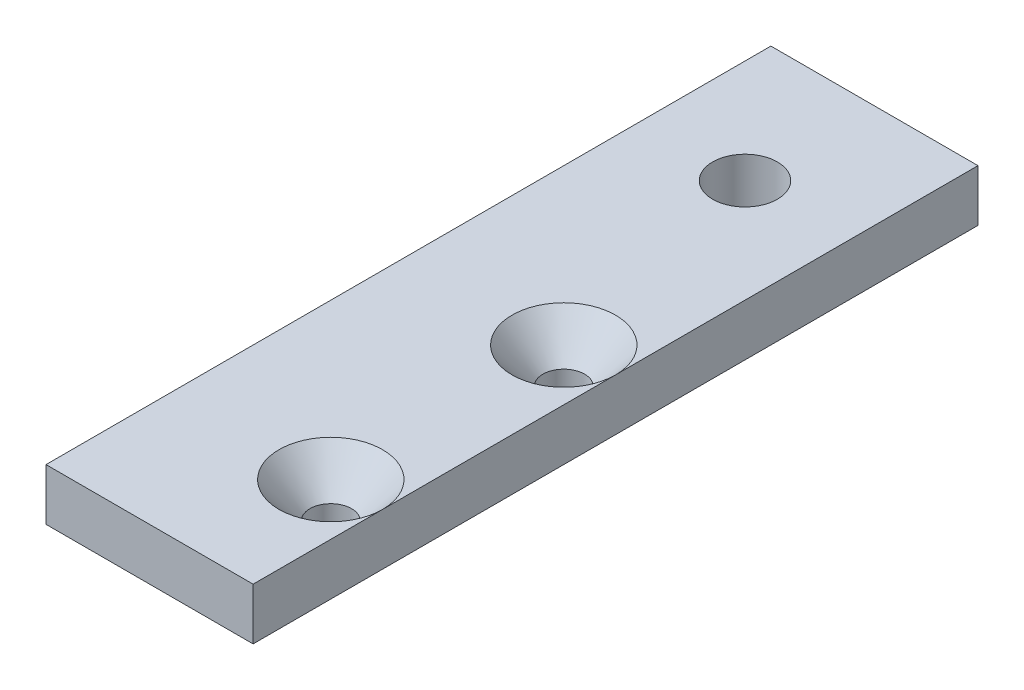
SolidWorks part; units mm, degrees
material "6061 Alloy"
ref_plane "Front Plane" through (0, 0, 0) normal (0, 0, 1) x (1, 0, 0)
ref_plane "Top Plane" through (0, 0, 0) normal (0, 1, 0) x (1, 0, 0)
ref_plane "Right Plane" through (0, 0, 0) normal (1, 0, 0) x (0, 0, -1)
sketch "Sketch1" plane through (0, 0, 0) normal (0, 1, 0) x (1, 0, 0)
  line L1 (0, 0) -> (-25.4, 0)
  line L2 (0, 0) -> (0, 88.9)
  line L3 (0, 88.9) -> (-25.4, 88.9)
  line L4 (-25.4, 0) -> (-25.4, 88.9)
  dimension "D1" = 88.9
  dimension "D2" = 25.4
extrude "Boss-Extrude1" add sketch "Sketch1" along normal blind 6.35
hole_wizard "1/4-20 Tapped Hole1" positions "Sketch2" profile "Sketch3" tap size "1/4-20" standard "ANSI Inch" end condition through all
sketch "Sketch2" plane through (0, 6.35, 0) normal (0, 1, 0) x (1, 0, 0)
  line L0 (-25.4, 0) -> (0, 0) construction
  line L1 (-6.35, 0) -> (-6.35, 88.9) construction
  line L2 (0, 88.9) -> (-25.4, 88.9) construction
  line L4 (0, 0) -> (0, 88.9) construction
  point P0 (-6.35, 15.875)
  point P2 (-6.35, 44.45)
  point P17 (0, 0)
  point P18 (0, 0)
  dimension "D1" = 15.875
  dimension "D2" = 6.35
  dimension "D3" = 44.45
sketch "Sketch3" plane through (-6.35, 6.35, -15.875) normal (1, 0, 0) x (0, 0, 1)
  line L0 (0, 0) -> (0, 6.35)
  line L1 (0, 6.35) -> (2.5527, 6.35)
  line L2 (2.5527, 6.35) -> (2.5527, 4.3683)
  line L3 (2.5527, 4.3683) -> (6.35, 0)
  line L5 (6.35, 0) -> (0, 0)
  line L6 (-2.5527, 4.3683) -> (-6.35, 0) construction
  line L11 (0, -6.35) -> (0, 107.95) construction
  dimension "Thru Tap Drill Dia." = 5.1054
  dimension "Thru Tap Drill Depth" = 6.35
  dimension "Near C'Sink Dia." = 12.7
  dimension "Near C'Sink Angle" = 82
cosmetic thread "Hole Thread2"
cosmetic thread "Hole Thread3"
hole_wizard "3/8-16 Tapped Hole1" positions "Sketch4" profile "Sketch5" tap size "3/8-16" standard "ANSI Inch" end condition through all
sketch "Sketch4" plane through (0, 6.35, 0) normal (0, 1, 0) x (1, 0, 0)
  line L0 (0, 88.9) -> (-25.4, 88.9) construction
  line L1 (0, 44.45) -> (0, 88.9) construction
  point P0 (-12.7, 73.025)
  dimension "D1" = 15.875
  dimension "D2" = 12.7
sketch "Sketch5" plane through (-12.7, 6.35, -73.025) normal (1, 0, 0) x (0, 0, 1)
  line L0 (0, 0) -> (0, 6.35)
  line L1 (0, 6.35) -> (3.9687, 6.35)
  line L2 (3.9687, 6.35) -> (3.9687, 0)
  line L5 (3.9687, 0) -> (0, 0)
  line L11 (0, -6.35) -> (0, 107.95) construction
  dimension "Thru Tap Drill Dia." = 7.9375
  dimension "Thru Tap Drill Depth" = 6.35
cosmetic thread "Hole Thread6"
